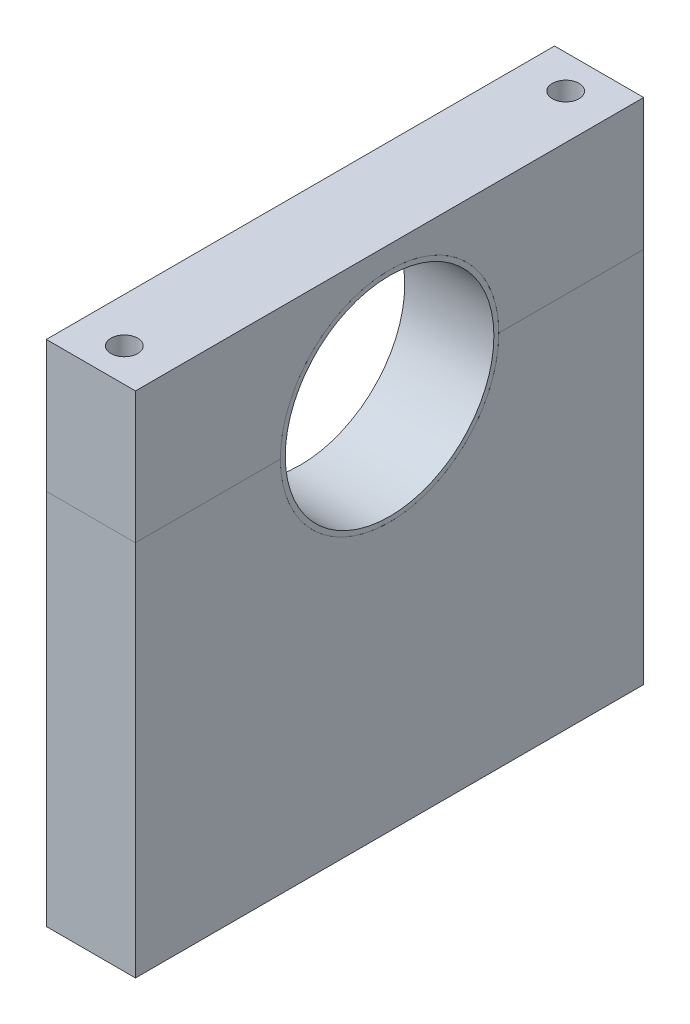
SolidWorks part; units mm, degrees
ref_plane "Front Plane" through (0, 0, 0) normal (0, 0, 1) x (1, 0, 0)
ref_plane "Top Plane" through (0, 0, 0) normal (0, 1, 0) x (1, 0, 0)
ref_plane "Right Plane" through (0, 0, 0) normal (1, 0, 0) x (0, 0, -1)
sketch "Sketch1" plane through (0, 0, 0) normal (0, 0, 1) x (1, 0, 0)
  line L0 (-44.079, 28.0482) -> (-34.079, 28.0482)
  line L1 (-34.079, 28.0482) -> (-34.079, 25.0482)
  line L2 (-34.079, 25.0482) -> (-29.079, 25.0482)
  line L3 (-29.079, 25.0482) -> (-29.079, 35.0482)
  line L4 (-29.079, 35.0482) -> (-49.079, 35.0482)
  line L5 (-49.079, 35.0482) -> (-49.079, 28.0482)
  line L6 (-49.079, 28.0482) -> (-46.079, 28.0482)
  line L7 (-46.079, 28.0482) -> (-46.079, 29.0482)
  line L8 (-46.079, 29.0482) -> (-44.079, 29.0482)
  line L9 (-44.079, 29.0482) -> (-44.079, 28.0482)
  line L10 (-85.0679, 10.5482) -> (6.0387, 10.5482) construction
  dimension "D1" = 24.5
  dimension "D2" = 20
  dimension "D3" = 17.5
  dimension "D4" = 2
  dimension "D5" = 10
  dimension "D6" = 3
  dimension "D7" = 1
  dimension "D8" = 3
revolve "Revolve1" add sketch "Sketch1" angle 360 about L10 other way angle 360
sketch "Sketch2" plane through (-49.079, 0, 0) normal (-1, 0, 0) x (0, 0, 1)
  line L0 (-24.5, 10.5482) -> (-57, 10.5482)
  line L1 (-57, -18.9518) -> (57, -18.9518)
  line L2 (-57, -18.9518) -> (-57, 40.0482)
  line L3 (-57, 40.0482) -> (57, 40.0482)
  line L4 (57, -18.9518) -> (57, 40.0482)
  line L5 (0, 40.0482) -> (0, -18.9518) construction
  line L6 (-57, 10.5482) -> (57, 10.5482) construction
  line L7 (24.5, 10.5482) -> (57, 10.5482)
  line L8 (-34.5, 40.0482) -> (-34.5, -18.9518) construction
  line L9 (-29.5, 40.0482) -> (-29.5, -18.9518) construction
  line L10 (29.5, 40.0482) -> (29.5, -18.9518) construction
  line L11 (34.5, 40.0482) -> (34.5, -18.9518) construction
  circle A0 centre (0, 10.5482) radius 24.5 construction
  circle A1 centre (0, 10.5482) radius 24.5 construction
  point P0 (0, 10.5482)
  point P7 (0, 35.0482)
  point P9 (0, -13.9518)
  point P10 (24.5, 10.5482)
  point P11 (-24.5, 10.5482)
  circle M9 centre (0, 10.5482) radius 24.5
  dimension "D1" = 49
  dimension "D2" = 5
  dimension "D3" = 5
  dimension "D4" = 114
  dimension "D6" = 5
  dimension "D7" = 5
  dimension "D8" = 22.5
extrude "Boss-Extrude2" add sketch "Sketch2" against normal up to surface (20 mm away) separate body contours L7 L4 L3 L2 L0 M9 region at (-49.079, 11.7257, -40.75) up to face at (-29.079, 10.5482, 24.5)
extrude "Boss-Extrude3" add sketch "Sketch2<3>" against normal up to surface (20 mm away) separate body contours L7 L0 L2 L1 L4 M9 region at (-49.079, -15.1294, 0) up to face at (-29.079, 10.5482, 24.5)
sketch "Sketch2<3>" plane through (-49.079, 0, 0) normal (-1, 0, 0) x (0, 0, 1) same geometry as "Sketch2"
sketch "Sketch3" plane through (0, 40.0482, 0) normal (0, 1, 0) x (1, 0, 0)
  line L0 (-39.079, -57) -> (-39.079, 57) construction
  line L1 (-29.079, -57) -> (-49.079, -57) construction
  line L2 (-29.079, 57) -> (-49.079, 57) construction
  circle A0 centre (-39.079, 49.5) radius 3
  circle A1 centre (-39.079, -49.5) radius 3
  dimension "D1" = 7.5
  dimension "D3" = 6
  dimension "D4" = 6
  dimension "D2" = 7.5
extrude "Cut-Extrude1" cut sketch "Sketch3" against normal up to surface (59 mm away) up to face at (-39.079, -18.9518, 0)
sketch "Sketch4" plane through (0, -18.9518, 0) normal (0, -1, 0) x (1, 0, 0)
  line L0 (-29.079, 57) -> (-29.079, -57) construction
  line L1 (-49.079, 57) -> (-29.079, 57)
  line L2 (-49.079, 57) -> (-49.079, -57)
  line L3 (-49.079, -57) -> (-29.079, -57)
  line L4 (-29.079, 57) -> (-29.079, -57)
  circle A0 centre (-39.079, 49.5) radius 3
  circle A1 centre (-39.079, -49.5) radius 3
  dimension "D1" = 114
extrude "Boss-Extrude5" add sketch "Sketch4" along normal blind 55.05
sketch "Sketch5" plane through (-29.079, 0, 0) normal (1, 0, 0) x (0, 0, -1)
  circle A0 centre (0, 10.5482) radius 23.4
extrude "Cut-Extrude2" cut sketch "Sketch5" against normal blind 34
